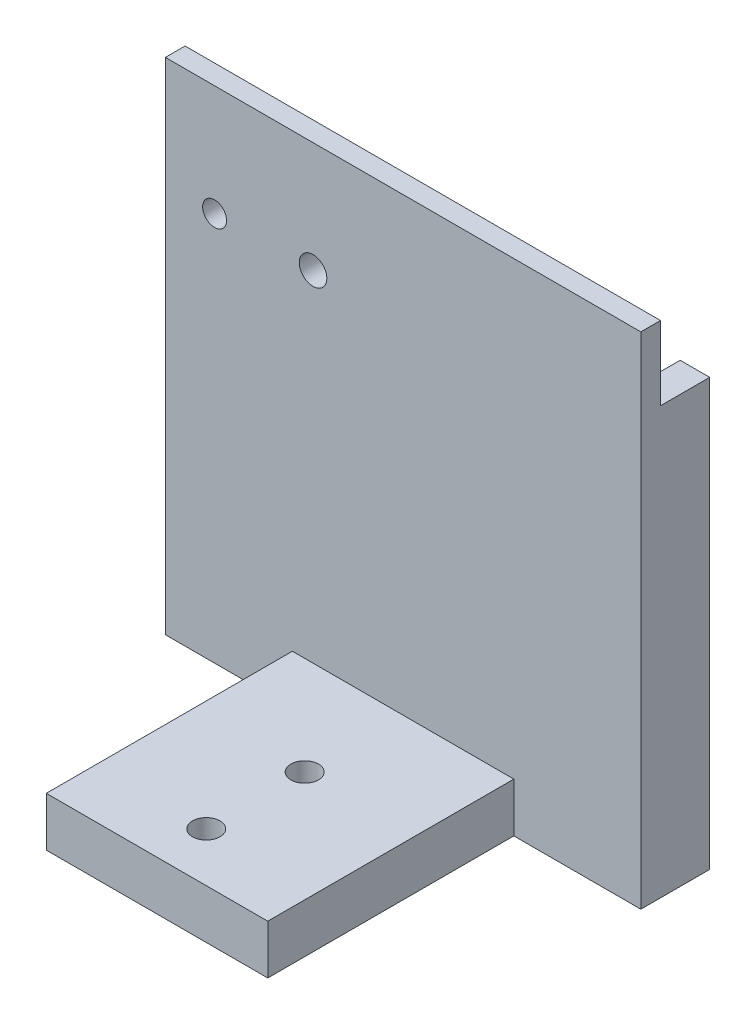
SolidWorks part; units mm, degrees
ref_plane "Front Plane" through (0, 0, 0) normal (0, 0, 1) x (1, 0, 0)
ref_plane "Top Plane" through (0, 0, 0) normal (0, 1, 0) x (1, 0, 0)
ref_plane "Right Plane" through (0, 0, 0) normal (1, 0, 0) x (0, 0, -1)
sketch "Sketch1" plane through (0, 0, 0) normal (0, 0, 1) x (1, 0, 0)
  line L0 (-17.15, 21.15) -> (17.15, 21.15) construction
  line L1 (21.15, -21.15) -> (-21.15, -21.15)
  line L2 (21.15, -21.15) -> (21.15, 21.15)
  line L3 (21.15, 21.15) -> (-21.15, 21.15)
  line L4 (-21.15, -21.15) -> (-21.15, 21.15)
  line L5 (-21.15, -17.15) -> (-21.15, 17.15) construction
  line L6 (21.15, 17.15) -> (21.15, -17.15) construction
  line L7 (17.15, -21.15) -> (-17.15, -21.15) construction
  line L9 (24.15, -22.15) -> (-24.15, -22.15)
  line L10 (24.15, -22.15) -> (24.15, 21.15)
  line L11 (24.15, 21.15) -> (-24.15, 21.15)
  line L12 (-24.15, -22.15) -> (-24.15, 21.15)
  point P16 (-21.15, 0)
  dimension "D1" = 0
  dimension "D2" = 0
  dimension "D3" = 0
  dimension "D4" = 0
  dimension "D5" = 3
  dimension "D6" = 3
  dimension "D7" = 1
  dimension "D8" = 0
extrude "Boss-Extrude1" add sketch "Sketch1" along normal blind 2 contours L4 L1 L2 L3 | L12 L9 L10 L11 L2 L1 L4 region at (21.7987, 0, 0) region at (0, 0, 0)
extrude "Boss-Extrude2" add sketch "Sketch1<3>" against normal blind 5 contours L12 L9 L10 L11 L2 L1 L4 region at (21.7987, 0, 0)
sketch "Sketch1<3>" plane through (0, 0, 0) normal (0, 0, 1) x (1, 0, 0) same geometry as "Sketch1"
sketch "Sketch2" plane through (0, 0, 2) normal (0, 0, 1) x (1, 0, 0)
  line L0 (24.15, -22.15) -> (-24.15, -22.15) construction
  line L1 (11.25, -22.15) -> (-11.25, -22.15)
  line L2 (11.25, -22.15) -> (11.25, -17.15)
  line L3 (11.25, -17.15) -> (-11.25, -17.15)
  line L4 (-11.25, -22.15) -> (-11.25, -17.15)
  line L5 (24.15, -22.15) -> (24.15, 21.15) construction
  dimension "D1" = 22.5
  dimension "D2" = 12.9
  dimension "D3" = 5
extrude "Boss-Extrude3" add sketch "Sketch2" along normal blind 25
sketch "Sketch3" plane through (0, 0, 2) normal (0, 0, 1) x (1, 0, 0)
  line L0 (-134.774, 28.649) -> (-80.274, 28.649) construction
  line L1 (-24.15, 6.149) -> (24.15, 6.149)
  line L2 (-24.15, 6.149) -> (-24.15, 28.649)
  line L3 (-24.15, 28.649) -> (24.15, 28.649)
  line L4 (24.15, 6.149) -> (24.15, 28.649)
  line L5 (24.15, -22.15) -> (24.15, 21.15) construction
  line L6 (-24.15, -22.15) -> (-24.15, 21.15) construction
  circle A0 centre (-19.15, 17.399) radius 1.2149
  circle A1 centre (-9.15, 17.399) radius 1.4
  dimension "D5" = 10
  dimension "D6" = 5
  dimension "D7" = 2.8
  dimension "D8" = 11.25
  dimension "D9" = 11.25
  dimension "D1" = 0
  dimension "D2" = 22.5
  dimension "D3" = 0
  dimension "D4" = 0
extrude "Boss-Extrude4" add sketch "Sketch3" against normal blind 2
sketch "Sketch4" plane through (0, -17.15, 0) normal (0, 1, 0) x (1, 0, 0)
  line L0 (11.25, -27) -> (-11.25, -27) construction
  line L1 (-11.25, -27) -> (-11.25, -2) construction
  circle A0 centre (0, -12) radius 1.4
  circle A1 centre (0, -22) radius 1.4
  dimension "D2" = 10
  dimension "D3" = 2.8
  dimension "D4" = 2.8
  dimension "D5" = 11.25
  dimension "D6" = 11.25
  dimension "D1" = 5
extrude "Cut-Extrude1" cut sketch "Sketch4" against normal through all
extrude "Cut-Extrude2" cut sketch "Sketch3<2>" against normal blind 2 contours A1 | A0 region at (-9.15, 17.399, 2)
sketch "Sketch3<2>" plane through (0, 0, 2) normal (0, 0, 1) x (1, 0, 0) same geometry as "Sketch3"
